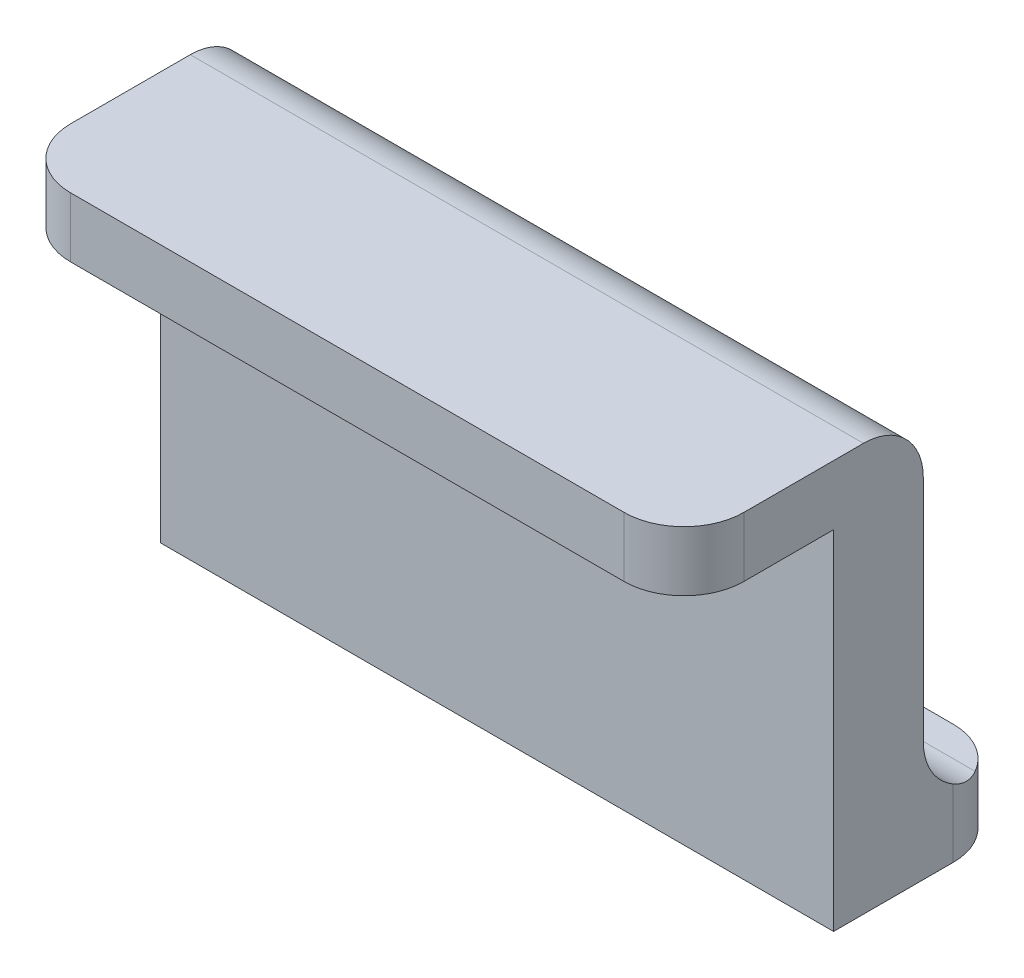
SolidWorks part; units mm, degrees
ref_plane "Front Plane" through (0, 0, 0) normal (0, 0, 1) x (1, 0, 0)
ref_plane "Top Plane" through (0, 0, 0) normal (0, 1, 0) x (1, 0, 0)
ref_plane "Right Plane" through (0, 0, 0) normal (1, 0, 0) x (0, 0, -1)
sketch "Sketch1" plane through (0, 0, 0) normal (0, 1, 0) x (1, 0, 0)
  line L1 (2, 0) -> (20.5, 0)
  line L2 (0, 2) -> (0, 5)
  line L3 (2, 7) -> (20.5, 7)
  line L4 (22.5, 2) -> (22.5, 5)
  arc A0 (20.5, 7) -> (22.5, 5) centre (20.5, 5) cw
  arc A1 (20.5, 0) -> (22.5, 2) centre (20.5, 2) ccw
  arc A2 (2, 0) -> (0, 2) centre (2, 2) cw
  arc A3 (0, 5) -> (2, 7) centre (2, 5) cw
  point P11 (0, 0)
  dimension "D1" = 2
  dimension "D2" = 2
  dimension "D3" = 22.5
  dimension "D4" = 7
extrude "Boss-Extrude1" add sketch "Sketch1" along normal blind 2
sketch "Sketch2" plane through (0, 2, 0) normal (0, 1, 0) x (1, 0, 0)
  line L0 (11.25, 0) -> (11.25, 10.7795) construction
  line L1 (2, 0) -> (20.5, 0) construction
  line L2 (22.5, 5) -> (22.5, 2)
  line L4 (0, 5) -> (0, 2) construction
  line L5 (20.5, 7) -> (2, 7) construction
  line L13 (0, 5) -> (0, 2)
  line L14 (20.5, 7) -> (2, 7)
  line L21 (21.4, 3.1) -> (21.4, 0.2139)
  line L22 (4.1, 6.1) -> (18.4, 6.1)
  line L23 (1.1, 0.2139) -> (1.1, 3.1)
  arc A0 (22.5, 2) -> (21.4, 0.2139) centre (20.5, 2) cw
  arc A1 (20.5, 7) -> (22.5, 5) centre (20.5, 5) cw
  arc A3 (2, 7) -> (0, 5) centre (2, 5) ccw construction
  arc A4 (0, 2) -> (2, 0) centre (2, 2) ccw construction
  arc A11 (2, 7) -> (0, 5) centre (2, 5) ccw
  arc A12 (0, 2) -> (1.1, 0.2139) centre (2, 2) ccw
  arc A15 (21.4, 3.1) -> (18.4, 6.1) centre (18.4, 3.1) ccw
  arc A16 (4.1, 6.1) -> (1.1, 3.1) centre (4.1, 3.1) ccw
  point P10 (22.5, 3.5)
  point P14 (11.25, 4.9)
  point P32 (11.25, 7)
  dimension "D2" = 0.9
  dimension "D3" = 3
  dimension "D1" = 1.1
extrude "Boss-Extrude2" add sketch "Sketch2" against normal blind 13.63
sketch "Sketch4" plane through (0, -11.63, 0) normal (0, -1, 0) x (1, 0, 0)
  line L5 (20.5, -7) -> (2, -7) construction
  line L8 (20.5, -7) -> (2, -7)
  line L9 (0, -5) -> (0, -9)
  line L10 (2, -11) -> (20.5, -11)
  line L11 (22.5, -9) -> (22.5, -5)
  arc A9 (20.5, -7) -> (22.5, -5) centre (20.5, -5) ccw construction
  arc A10 (0, -5) -> (2, -7) centre (2, -5) ccw construction
  arc A11 (20.5, -7) -> (22.5, -5) centre (20.5, -5) ccw
  arc A12 (0, -5) -> (2, -7) centre (2, -5) ccw
  arc A13 (0, -9) -> (2, -11) centre (2, -9) ccw
  arc A14 (20.5, -11) -> (22.5, -9) centre (20.5, -9) ccw
  dimension "D1" = 2
  dimension "D2" = 4
extrude "Boss-Extrude3" add sketch "Sketch4" against normal blind 2
sketch "Sketch5" plane through (0, 0, 0) normal (0, -1, 0) x (1, 0, 0)
  line L0 (2, 0) -> (20.5, 0) construction
  line L1 (0, 0) -> (22.5, 0)
  line L2 (0, 0) -> (0, -6.1)
  line L3 (0, -6.1) -> (22.5, -6.1)
  line L4 (22.5, 0) -> (22.5, -6.1)
  line L5 (4.1, -6.1) -> (18.4, -6.1) construction
  line L6 (0, -9) -> (0, -2) construction
  line L7 (22.5, -2) -> (22.5, -9) construction
extrude "Cut-Extrude1" cut sketch "Sketch5" along normal through all
sketch "Sketch6" plane through (0, -9.63, 0) normal (0, 1, 0) x (1, 0, 0)
  line L0 (0, 6.1) -> (0, 9) construction
  line L1 (22.5, 5) -> (0, 5)
  line L2 (22.5, 5) -> (22.5, 8)
  line L3 (22.5, 8) -> (0, 8)
  line L4 (0, 5) -> (0, 8)
  dimension "D1" = 3
extrude "Boss-Extrude4" add sketch "Sketch6" along normal up to surface and the other way up to surface up to face at (11.25, 2, -3.5) other way up to face at (11.25, -11.63, -8.8381)
fillet "Fillet1" radius 2 2 edges at (11.25, -9.63, -8) (11.25, 2, -8)
